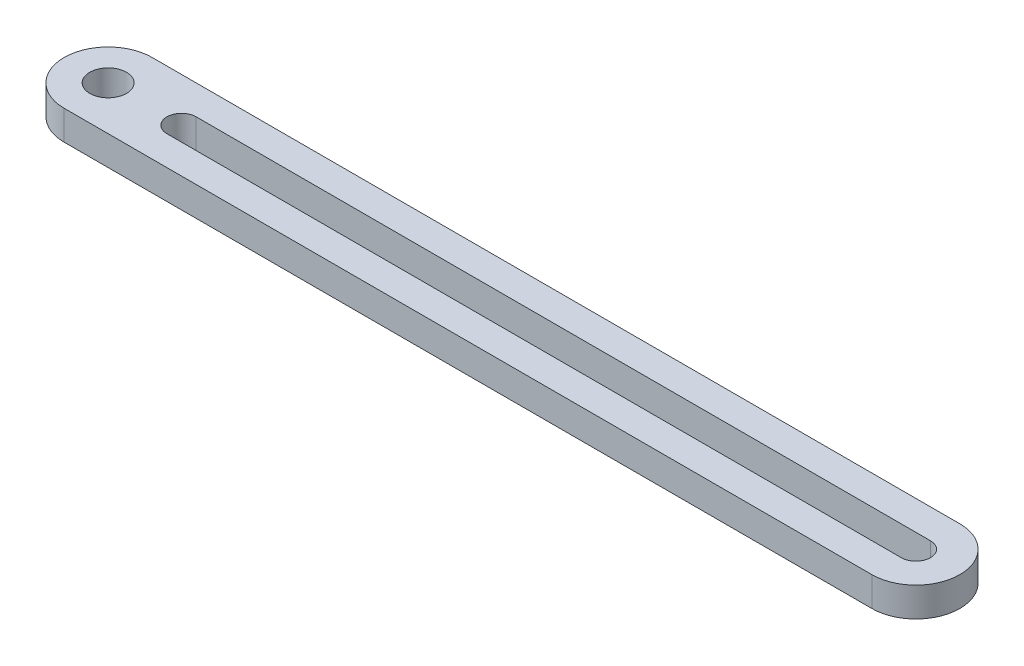
SolidWorks part; units mm, degrees
ref_plane "Front Plane" through (0, 0, 0) normal (0, 0, 1) x (1, 0, 0)
ref_plane "Top Plane" through (0, 0, 0) normal (0, 1, 0) x (1, 0, 0)
ref_plane "Right Plane" through (0, 0, 0) normal (1, 0, 0) x (0, 0, -1)
sketch "Sketch1" plane through (0, 0, 0) normal (0, 1, 0) x (1, 0, 0)
  line L0 (10, 0) -> (110, 0) construction
  line L1 (10, 1.9919) -> (110, 1.9919)
  line L2 (10, -1.9919) -> (110, -1.9919)
  line L3 (0, 0) -> (110, 0) construction
  line L4 (0, 5.9919) -> (110, 5.9919)
  line L5 (0, -5.9919) -> (110, -5.9919)
  circle A0 centre (0, 0) radius 2.5
  arc A1 (10, 1.9919) -> (10, -1.9919) centre (10, 0) ccw
  arc A2 (110, -1.9919) -> (110, 1.9919) centre (110, 0) ccw
  arc A3 (0, 5.9919) -> (0, -5.9919) centre (0, 0) ccw
  arc A4 (110, -5.9919) -> (110, 5.9919) centre (110, 0) ccw
  point P5 (60, 0)
  point P10 (55, 0)
  dimension "D1" = 5
  dimension "D2" = 10
  dimension "D3" = 100
  dimension "D4" = 4
extrude "Boss-Extrude1" add sketch "Sketch1" along normal blind 4
